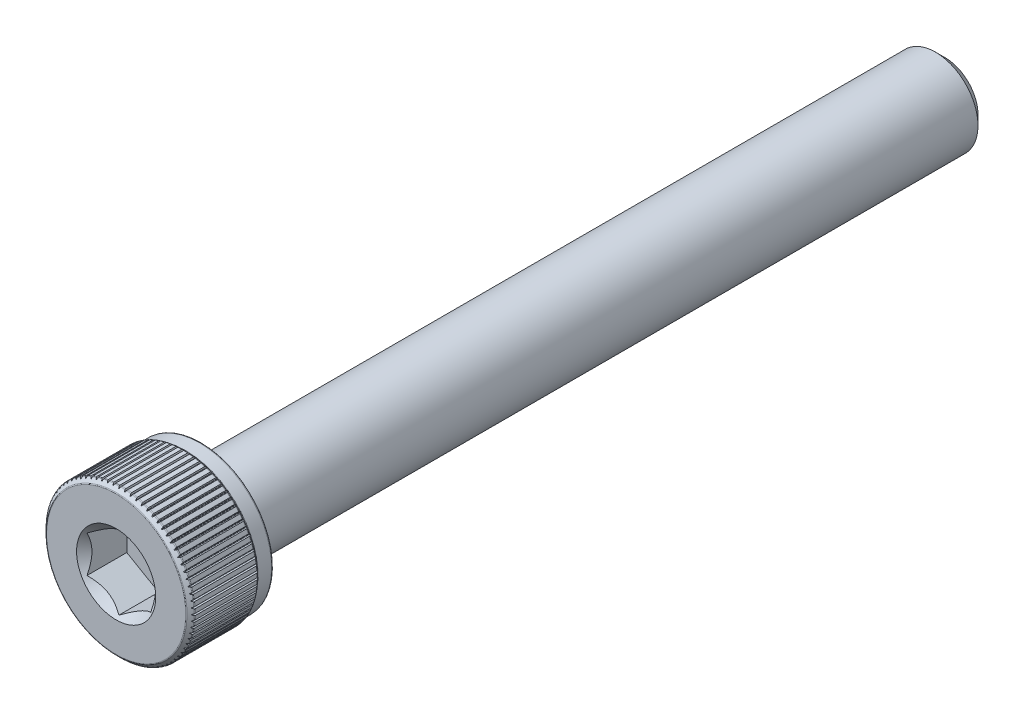
SolidWorks part; units mm, degrees
ref_plane "Front Plane" through (0, 0, 0) normal (0, 0, 1) x (1, 0, 0)
ref_plane "Top Plane" through (0, 0, 0) normal (0, 1, 0) x (1, 0, 0)
ref_plane "Right Plane" through (0, 0, 0) normal (1, 0, 0) x (0, 0, -1)
sketch "Sketch1" plane through (0, 0, 0) normal (1, 0, 0) x (0, 0, -1)
  line L0 (-19.5, 0) -> (19.5, 0) construction
  line L1 (19.5, 0) -> (19.5, 1.5453) construction
  line L2 (19.5, 1.5453) -> (19.0453, 2) construction
  line L3 (19.0453, 2) -> (18.975, 2) construction
  line L4 (18.975, 2) -> (-15.5, 2) construction
  line L5 (-15.5, 2) -> (-15.5, 3.5) construction
  line L6 (-15.5, 3.5) -> (-19.5, 3.5) construction
  line L7 (-19.5, 3.5) -> (-19.5, 0) construction
  line L8 (19.5, 1.5453) -> (19.5, 2) construction
  line L9 (19.4563, 2.0758) -> (19.8063, 1.4696) construction
  line L10 (19.8063, 1.4696) -> (20.1563, 2.0758) construction
  line L11 (20.1563, 2.0758) -> (19.4563, 2.0758) construction
  line L12 (19.8063, 2.0758) -> (19.8063, 2) construction
  line L13 (19.8063, 1.4696) -> (19.8063, 1.5453) construction
  line L14 (19.7625, 1.5453) -> (19.85, 1.5453) construction
  line L15 (19.5, 2) -> (20.1125, 2) construction
  line L16 (19.4781, 2.0379) -> (20.1344, 2.0379) construction
  line L17 (19.5, 0) -> (19.5, -2) construction
  line L18 (-15.7, 3.5) -> (-15.5, 3.3) construction
  line L19 (-19.3, 3.5) -> (-19.5, 3.3) construction
  line L20 (-15.5, 2) -> (-15.5, 0) construction
  line L21 (-15.5, 1) -> (-3.8333, 1) construction
  line L22 (-3.8333, 1) -> (7.8333, 1) construction
  line L23 (7.8333, 1) -> (19.5, 1) construction
  line L24 (-3.8333, 1) -> (-3.8333, 2) construction
  line L25 (-3.8333, 2) -> (-3.8333, 3.5) construction
  line L26 (7.8333, 1) -> (7.8333, 3.5) construction
  point P0 (-19.5, 1.5)
  point P3 (17.75, 2)
  point P4 (0, 0)
  point P18 (7.8333, 2)
  point P22 (19.8063, 1.5453)
  point P24 (18.975, 2)
  point P25 (19.8063, 2)
  point P28 (19.8063, 2.0379)
  point P29 (17.75, -2)
  point P30 (-3.8333, 2)
  point P31 (-17.5, 3.5)
  point P37 (-16.2, 3.5)
  point P38 (-19.2, 3.5)
  point P45 (-3.8333, 1)
  point P46 (7.8333, 1)
  dimension "D1" = 45
  dimension "D2" = 0.0875
  dimension "D7" = 0.2
  dimension "D8" = 0.2
  dimension "D9" = 0.2
  dimension "D10" = 0.1
  dimension "D11" = 0.5
  dimension "Drive Size" = 3
  dimension "Head Diameter" = 7
  dimension "Head Height" = 4
  dimension "Thread Pitch" = 0.7
  dimension "Thread Dia" = 4
  dimension "Length" = 35
  dimension "D12" = 0.525
  dimension "D4" = 1.75
  dimension "Key Engagement" = 2
sketch "Sketch2" plane through (0, 0, 0) normal (1, 0, 0) x (0, 0, -1)
  line L0 (-19.5, 0) -> (-19.5, 3.2741)
  line L1 (-19.2741, 3.5) -> (-16.3759, 3.5)
  line L2 (-15.5, 3.3125) -> (-15.5, 2.2)
  line L4 (19.0453, 2) -> (19.5, 1.5453)
  line L5 (19.5, 1.5453) -> (19.5, 0)
  line L6 (-15.5, 3.5) -> (-19.5, 3.5) construction
  line L7 (19.5, 0) -> (-19.5, 0)
  line L8 (-19.3, 3.5) -> (-19.5, 3.3) construction
  line L10 (-19.3183, 3.4817) -> (-19.4817, 3.3183)
  line L12 (-16.2241, 3.4) -> (-15.5875, 3.4)
  line L14 (-15.7, 3.5) -> (-15.5, 3.3) construction
  line L15 (-16.3317, 3.4817) -> (-16.2683, 3.4183)
  line L17 (-15.5, 2) -> (-15.5, 3.5) construction
  line L19 (-15.3, 2) -> (19.0453, 2)
  line L20 (18.975, 2) -> (-15.5, 2) construction
  arc A0 (-15.5875, 3.4) -> (-15.5, 3.3125) centre (-15.5875, 3.3125) cw
  arc A1 (-15.5, 2.2) -> (-15.3, 2) centre (-15.3, 2.2) ccw
  arc A2 (-19.3183, 3.4817) -> (-19.2741, 3.5) centre (-19.2741, 3.4375) cw
  arc A3 (-19.4817, 3.3183) -> (-19.5, 3.2741) centre (-19.4375, 3.2741) ccw
  arc A4 (-16.3317, 3.4817) -> (-16.3759, 3.5) centre (-16.3759, 3.4375) ccw
  arc A5 (-16.2683, 3.4183) -> (-16.2241, 3.4) centre (-16.2241, 3.4625) ccw
  point P22 (-15.6, 3.4)
  point P37 (-16.25, 3.4)
  dimension "D2" = 0.0875
  dimension "D3" = 0.2
  dimension "D4" = 0.0625
  dimension "D1" = 0.75
revolve "Revolve1" add sketch "Sketch2" angle 360 about L7
sketch "Sketch3" plane through (0, 0, 19.5) normal (0, 0, 1) x (1, 0, 0)
  line L1 (1.5, -0.866) -> (1.5, 0.866)
  line L2 (1.5, 0.866) -> (0, 1.7321)
  line L3 (0, 1.7321) -> (-1.5, 0.866)
  line L4 (-1.5, 0.866) -> (-1.5, -0.866)
  line L5 (-1.5, -0.866) -> (0, -1.7321)
  line L6 (0, -1.7321) -> (1.5, -0.866)
  circle A0 centre (0, 0) radius 1.5 construction
  circle A1 centre (0, 0) radius 3.5 construction
  circle A2 centre (0, 0) radius 3.5 construction
  circle A3 centre (0, 0) radius 1.7321 construction
  dimension "D1" = 3.4641
extrude "Cut-Extrude1" cut sketch "Sketch3" against normal up to vertex (2 mm away) up to point (0, 3.5, 17.5)
sketch "Sketch4" plane through (0, 0, 19.5) normal (0, 0, 1) x (1, 0, 0)
  circle A0 centre (0, 0) radius 1.862
  dimension "D1" = 3.7239
extrude "Cut-Extrude2" cut sketch "Sketch4" against normal up to vertex (2 mm away) draft 45 up to point (0, 3.5, 17.5)
sketch "Sketch6" [suppressed] plane through (0, 0, -19.5) normal (0, 0, -1) x (-1, 0, 0)
  circle A0 centre (0, 0) radius 2
curve "Helix/Spiral1" [suppressed] pitch 0.7 height 35.7 turns 51
sketch "Sketch7" [suppressed] plane through (0, 0, 0) normal (1, 0, 0) x (0, 0, -1)
  line L0 (19.4781, 2.0379) -> (20.1344, 2.0379)
  line L1 (20.1344, 2.0379) -> (19.85, 1.5453)
  line L2 (19.85, 1.5453) -> (19.7625, 1.5453)
  line L3 (19.7625, 1.5453) -> (19.4781, 2.0379)
sweep "Cut-Sweep1" [suppressed] cut profiles "Sketch7" path "Helix/Spiral1"
sketch "Sketch8" [suppressed] plane through (0, 0, 0) normal (1, 0, 0) x (0, 0, -1)
  line L0 (-17.5, 0) -> (-17.5, 2.2)
  line L1 (-17.5, 0.866) -> (-17.5, 1.7321) construction
  line L2 (-15.3, 2) -> (-15.15, 2)
  line L3 (-15.5, 2.2) -> (-17.5, 2.2)
  line L4 (-15.15, 2) -> (-13.9953, 0)
  line L5 (-13.9953, 0) -> (-17.5, 0)
  line L7 (-19.5, 0) -> (19.5, 0) construction
  line L8 (-15.5, 2) -> (-15.5, 3.5) construction
  arc A0 (-15.5, 2.2) -> (-15.3, 2) centre (-15.3, 2.2) ccw construction
  arc A1 (-15.5, 2.2) -> (-15.3, 2) centre (-15.3, 2.2) ccw
  dimension "D1" = 60
  dimension "D2" = 0.35
revolve "Revolve2" [suppressed] add sketch "Sketch8" angle 360 about L5
sketch "Sketch9" plane through (0, 0, 19.5) normal (0, 0, 1) x (1, 0, 0)
  line L0 (-0.016, 3.4357) -> (-0.0875, 3.5954)
  line L1 (-0.0875, 3.5954) -> (0.0875, 3.5954)
  line L2 (0.0875, 3.5954) -> (0.016, 3.4357)
  line L3 (0, 3.5) -> (0, 3.3) construction
  line L4 (0, 0) -> (-0.0875, 3.5954) construction
  line L5 (0.0875, 3.5954) -> (0, 0) construction
  circle A0 centre (0, 0) radius 3.4 construction
  arc A4 (-0.016, 3.4357) -> (0.016, 3.4357) centre (0, 3.4428) ccw
  point P10 (0, 3.4)
  point P19 (0, 3.4)
  dimension "D2" = 0.0175
  dimension "D1" = 0.175
  dimension "D3" = 2.788
extrude "Cut-Extrude3" cut sketch "Sketch9" against normal through all
pattern_circular "CirPattern1" count 80 over 360 about axis through (0, 0, 19.2741) along (0, 0, -1) of "Cut-Extrude3"
equation "\"D2@Sketch1\" = \"Thread Pitch@Sketch1\" / 8"
equation "\"D4@Helix/Spiral1\" = \"Thread Pitch@Sketch1\""
equation "\"D7@Sketch1\" = \"Head Height@Sketch1\" * .05"
equation "\"D8@Sketch1\"=\"D7@Sketch1\""
equation "\"D9@Sketch1\"=\"D7@Sketch1\""
equation "\"D10@Sketch1\"=\"D7@Sketch1\"/2"
equation "\"D11@Sketch1\"=\"D10@Sketch1\"*5"
equation "\"D4@Sketch1\"=\"Thread Pitch@Sketch1\"*2.5"
equation "\"D12@Sketch1\"=\"Thread Pitch@Sketch1\"*.75"
equation "\"D3@Helix/Spiral1\"=\"Length@Sketch1\"+\"Thread Pitch@Sketch1\""
equation "\"D1@Sketch2\"=\"Head Height@Sketch1\"*0.1875"
equation "\"D2@Sketch2\"=\"Head Diameter@Sketch1\"*0.0125"
equation "\"D3@Sketch2\"=\"Thread Dia@Sketch1\"*0.05"
equation "\"D1@Sketch9\"=\"Head Diameter@Sketch1\"*0.025"
equation "\"D2@Sketch9\"=\"D1@Sketch9\"*0.1"
equation "\"D2@Sketch8\"=\"Thread Pitch@Sketch1\"*00.5"
equation "\"D4@Sketch2\"=\"D8@Sketch1\"*0.3125"
equation "\"D1@CirPattern1\"=int ((360/\"D3@Sketch9\")*0.625)"
equation "\"D1@Sketch4\"=\"D1@Sketch3\" * 01.075"
